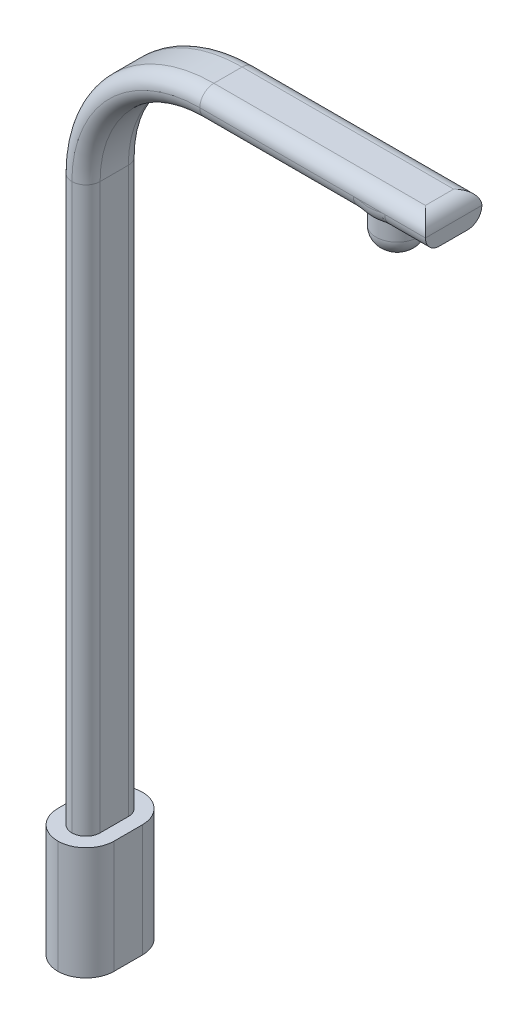
SolidWorks part; units mm, degrees
ref_plane "Alzado" through (0, 0, 0) normal (0, 0, 1) x (1, 0, 0)
ref_plane "Planta" through (0, 0, 0) normal (0, 1, 0) x (1, 0, 0)
ref_plane "Vista lateral" through (0, 0, 0) normal (1, 0, 0) x (0, 0, -1)
sketch "Croquis7" plane through (0, 0, 0) normal (0, 0, 1) x (1, 0, 0)
  line L0 (-5, 200) -> (5, 0) construction
  line L1 (-10, -40) -> (10, -40)
  line L2 (-10, -40) -> (-10, 0)
  line L3 (-10, 0) -> (10, 0)
  line L4 (10, -40) -> (10, 0)
  line L5 (-5, 0) -> (5, 0)
  line L6 (-5, 0) -> (-5, 200)
  line L8 (5, 0) -> (5, 200)
  line L17 (45.3516, 240.3516) -> (125.3516, 240.3516)
  line L18 (125.3516, 240.3516) -> (125.3516, 250.3516)
  line L19 (125.3516, 250.3516) -> (45.3516, 250.3516)
  arc A2 (45.3516, 250.3516) -> (-5, 200) centre (45.3516, 200) ccw
  arc A3 (45.3516, 240.3516) -> (5, 200) centre (45.3516, 200) ccw
  point P4 (0, 0)
  point P10 (0, 100)
  point P14 (5, 200)
  point P15 (-5, 200)
  dimension "D5" = 10
  dimension "D6" = 40.3516
  dimension "D1" = 40
  dimension "D2" = 20
  dimension "D3" = 10
  dimension "D4" = 200
extrude "Saliente-Extruir7" add sketch "Croquis7" along normal blind 20 contours L19 A2 L6 L5 L8 A3 L17 L18 | L2 L1 L4 L3
sketch "Croquis10" plane through (0, 0, 20) normal (0, 0, 1) x (1, 0, 0)
  line L1 (-10, 0) -> (10, 0)
  line L2 (-10, 0) -> (-10, -40)
  line L3 (-10, -40) -> (10, -40)
  line L4 (10, 0) -> (10, -40)
extrude "Saliente-Extruir8" add sketch "Croquis10" along normal blind 5 and the other way blind 25
sketch "Croquis11" plane through (0, 240.3516, 0) normal (0, -1, 0) x (1, 0, 0)
  line L0 (125.3516, 20) -> (125.3516, 0) construction
  circle A0 centre (105.3516, 10) radius 7.5
  point P4 (125.3516, 10)
  dimension "D1" = 20
  dimension "D2" = 15
extrude "Saliente-Extruir9" add sketch "Croquis11" along normal blind 12
fillet "Redondeo6" radius 6 1 edges at (105.3516, 228.3516, 2.5)
fillet "Redondeo7" radius 10 4 edges at (10, -20, -5) (10, -20, 25) (-10, -20, 25) (-10, -20, -5)
fillet "Redondeo10" radius 5 13 edges at (85.3516, 250.3516, 0) (9.7476, 235.6039, 0) (85.3516, 250.3516, 20) (9.7476, 235.6039, 20) (85.3516, 240.3516, 20) (16.8187, 228.5329, 20) (85.3516, 240.3516, 0) (16.8187, 228.5329, 0) (125.3516, 250.3516, 10) (-5, 100, 0) (-5, 100, 20) (5, 100, 20) (5, 100, 0)
